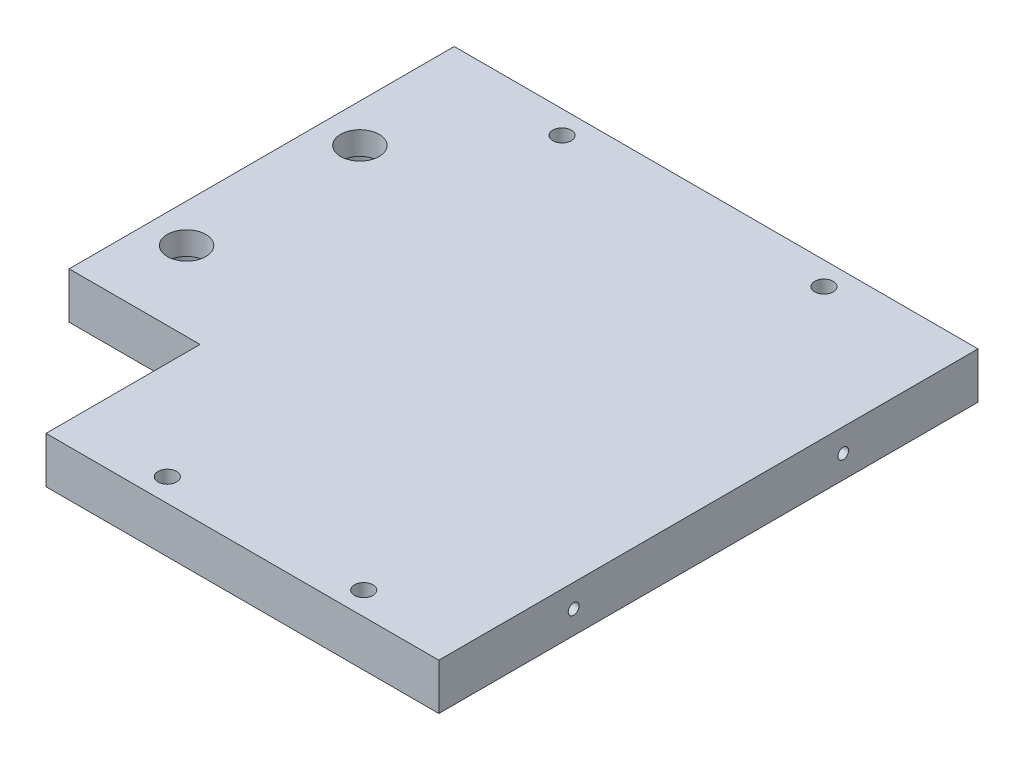
SolidWorks part; units mm, degrees
ref_plane "前视基准面" through (0, 0, 0) normal (0, 0, 1) x (1, 0, 0)
ref_plane "上视基准面" through (0, 0, 0) normal (0, 1, 0) x (1, 0, 0)
ref_plane "右视基准面" through (0, 0, 0) normal (1, 0, 0) x (0, 0, -1)
other "Configuration Table"
sketch "草图1" plane through (0, 0, 0) normal (0, 1, 0) x (1, 0, 0)
  line L1 (-17, -12.5) -> (17, -12.5)
  line L2 (-17, -12.5) -> (-17, 12.5)
  line L3 (-17, 12.5) -> (17, 12.5)
  line L4 (17, -12.5) -> (17, 12.5)
  line L5 (-17, -12.5) -> (17, 12.5) construction
  line L6 (-17, 12.5) -> (17, -12.5) construction
  line L7 (17, -12.5) -> (-8.5, -12.5)
  line L8 (17, -12.5) -> (17, -22.5)
  line L9 (17, -22.5) -> (-8.5, -22.5)
  line L10 (-8.5, -12.5) -> (-8.5, -22.5)
  point P0 (0, 0)
  dimension "D3" = 25.5
  dimension "D1" = 34
  dimension "D2" = 10
  dimension "D5" = 25
extrude "凸台-拉伸1" add sketch "草图1" along normal blind 3 contours L3 L4 L1 L2 | L8 L9 L10 L7
sketch "草图2" plane through (0, 0, 0) normal (0, -1, 0) x (-1, 0, 0)
  line L0 (-17, -22.5) -> (8.5, -22.5) construction
  line L1 (-17, -21) -> (-10.625, -21) construction
  line L2 (-17, -22.5) -> (-17, 12.5) construction
  line L3 (-10.625, -21) -> (-4.25, -21) construction
  line L4 (-4.25, -21) -> (2.125, -21) construction
  line L5 (2.125, -21) -> (8.5, -21) construction
  line L6 (8.5, -12.5) -> (8.5, -22.5) construction
  line L7 (17, 12.5) -> (-17, 12.5) construction
  line L8 (-17, 11) -> (-8.5, 11) construction
  line L9 (-8.5, 11) -> (0, 11) construction
  line L10 (0, 11) -> (8.5, 11) construction
  line L11 (8.5, 11) -> (17, 11) construction
  line L12 (17, -12.5) -> (17, 12.5) construction
  circle A0 centre (14.5, 3.875) radius 2
  circle A1 centre (14.5, -7.375) radius 2
  circle A2 centre (14.5, -7.375) radius 1.25
  circle A3 centre (14.5, 3.875) radius 1.25
  circle A4 centre (-10.625, -21) radius 1
  circle A5 centre (2.125, -21) radius 1
  circle A6 centre (-10.625, -21) radius 0.6
  circle A7 centre (2.125, -21) radius 0.6
  circle A8 centre (-8.5, 11) radius 0.6
  circle A9 centre (8.5, 11) radius 0.6
  circle A10 centre (-8.5, 11) radius 1
  circle A11 centre (8.5, 11) radius 1
  dimension "D1" = 2.5
  dimension "D2" = 4
  dimension "D4" = 1.2
  dimension "D5" = 2
  dimension "D6" = 1.2
  dimension "D7" = 2
  dimension "D3" = 1.5
  dimension "D8" = 1.5
extrude "切除-拉伸1" cut sketch "草图2" against normal through all contours A3 | A2 | A6 | A7 | A8 | A9
extrude "切除-拉伸2" cut sketch "草图2<3>" against normal blind 1.5 contours A1 | A0 | A4 | A5 | A10 | A11
sketch "草图2<3>" plane through (0, 0, 0) normal (0, -1, 0) x (-1, 0, 0) same geometry as "草图2"
sketch "草图3" plane through (17, 0, 0) normal (1, 0, 0) x (0, 0, -1)
  circle A0 centre (3.75, 1.5) radius 0.35
  circle A1 centre (-13.75, 1.5) radius 0.35
  point P4 (0, 0)
  dimension "D1" = 0.7
extrude "切除-拉伸3" cut sketch "草图3" against normal blind 3
